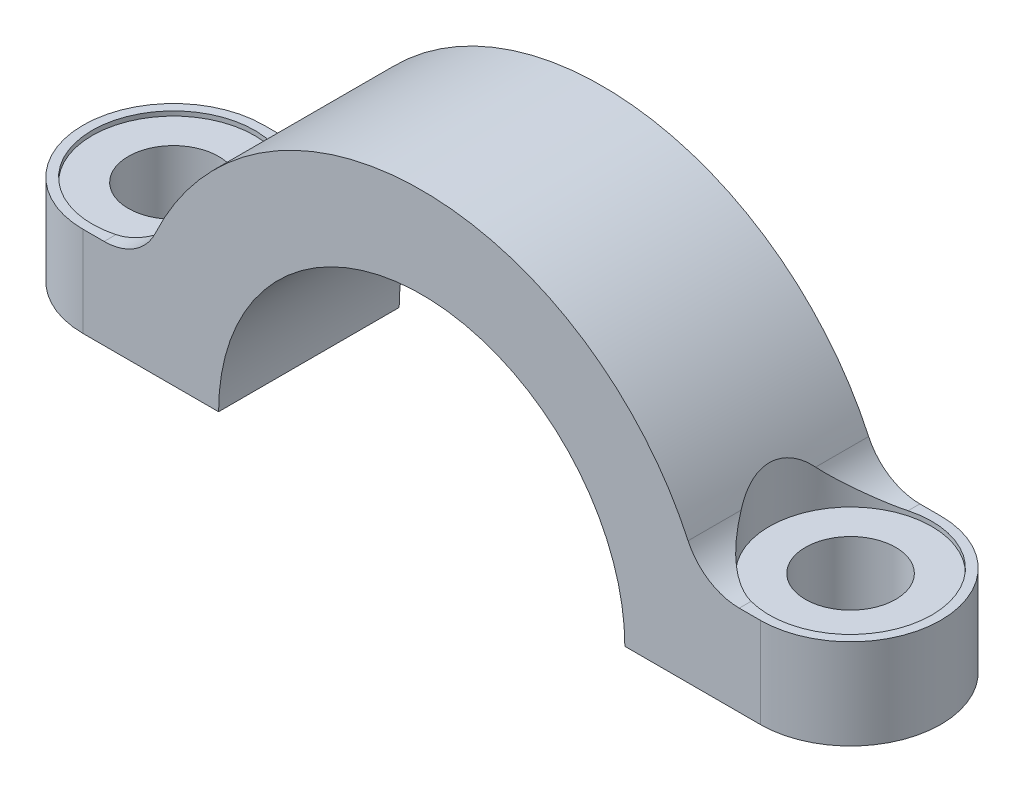
SolidWorks part; units mm, degrees
ref_plane "Front Plane" through (0, 0, 0) normal (0, 0, 1) x (1, 0, 0)
ref_plane "Top Plane" through (0, 0, 0) normal (0, 1, 0) x (1, 0, 0)
ref_plane "Right Plane" through (0, 0, 0) normal (1, 0, 0) x (0, 0, -1)
sketch "Sketch1" plane through (0, 0, 0) normal (0, 0, 1) x (1, 0, 0)
  line L0 (-19, 0) -> (-9, 0)
  line L1 (9, 0) -> (19, 0)
  line L2 (-9, 0) -> (9, 0) construction
  line L3 (0, -9) -> (0, 9) construction
  line L4 (-19, 4) -> (-14.0712, 4)
  line L5 (14.0712, 4) -> (19, 4)
  line L6 (-19, 4) -> (-19, 0)
  line L7 (19, 4) -> (19, 0)
  line L8 (12.3693, 4) -> (19, 4) construction
  line L9 (-19, 4) -> (-12.3693, 4) construction
  arc A0 (9, 0) -> (-9, 0) centre (0, 0) ccw
  arc A1 (11.8017, 5.4516) -> (-11.8017, 5.4516) centre (0, 0) ccw
  arc A2 (12.3693, 4) -> (-12.3693, 4) centre (0, 0) ccw construction
  arc A3 (11.8017, 5.4516) -> (14.0712, 4) centre (14.0712, 6.5) ccw
  arc A4 (-14.0712, 4) -> (-11.8017, 5.4516) centre (-14.0712, 6.5) ccw
  point P4 (0, 0)
  point P9 (0, 0)
  point P11 (0, 0)
  dimension "D1" = 9
  dimension "D5" = 2.5
  dimension "D2" = 19
  dimension "D3" = 19
  dimension "D4" = 4
extrude "Boss-Extrude1" add sketch "Sketch1" along normal mid plane 8
sketch "Sketch2" plane through (0, 0, 0) normal (0, 1, 0) x (1, 0, 0)
  line L0 (0, -4) -> (0, 4) construction
  line L1 (11.8017, 4) -> (-11.8017, 4) construction
  line L2 (-15, 0) -> (15, 0) construction
  circle A0 centre (15, 0) radius 2
  circle A1 centre (-15, 0) radius 2
  point P6 (0, 0)
  point P10 (0, 0)
  dimension "D2" = 4
  dimension "D1" = 30
extrude "Cut-Extrude1" cut sketch "Sketch2" along normal through all
fillet "Fillet1" 2 edges at (19, 2, 4) (19, 2, -4) type full round first side face at (0, 4.2788, 4) second side face at (0, 4.2788, -4) middle face at (19, 2, 0)
fillet "Fillet2" 2 edges at (-19, 2, -4) (-19, 2, 4) type full round first side face at (-0.8, 4.2788, -4) second side face at (-0.8, 4.2788, 4) middle face at (-19, 2, 0)
sketch "Sketch3" plane through (0, 0, 0) normal (0, 1, 0) x (1, 0, 0)
  circle A0 centre (-15, 0) radius 3.6
  circle A1 centre (15, 0) radius 3.6
  arc A2 (-15, 4) -> (-15, -4) centre (-15, 0) ccw construction
  arc A3 (15, -4) -> (15, 4) centre (15, 0) ccw construction
  dimension "D1" = 7.2
extrude "Cut-Extrude2" cut sketch "Sketch3" along normal through all from offset 3.8
